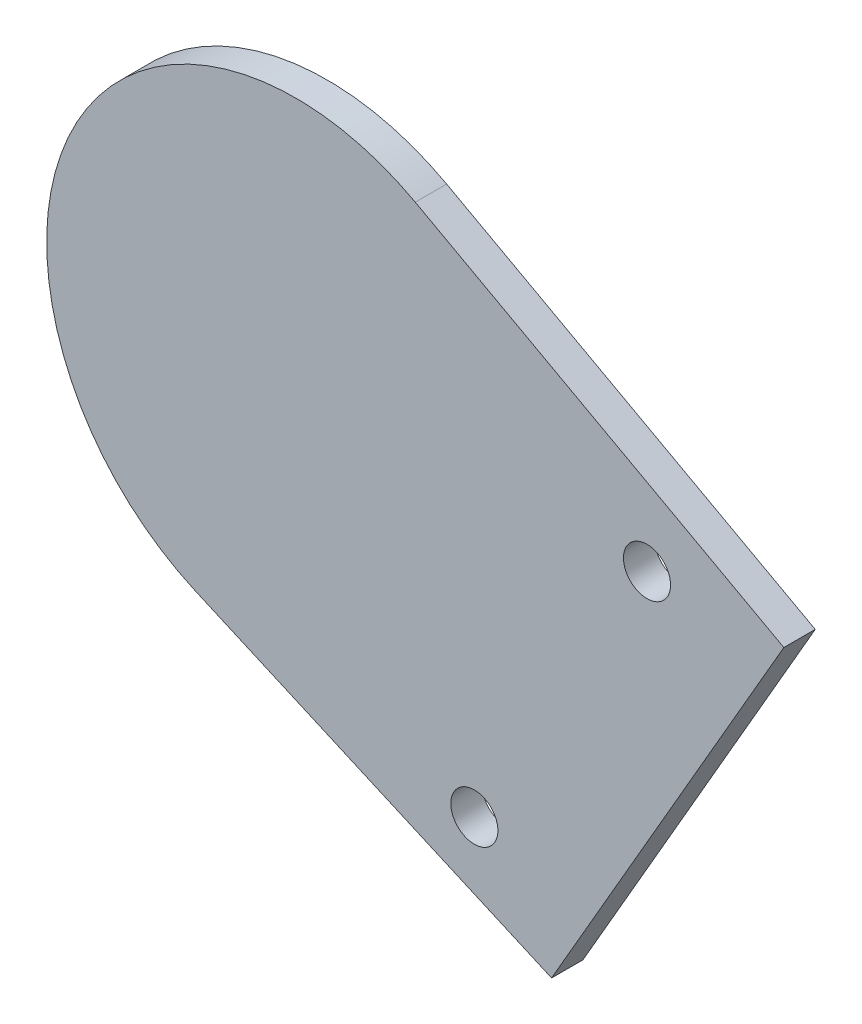
SolidWorks part; units mm, degrees
ref_plane "Front Plane" through (0, 0, 0) normal (0, 0, 1) x (1, 0, 0)
ref_plane "Top Plane" through (0, 0, 0) normal (0, 1, 0) x (1, 0, 0)
ref_plane "Right Plane" through (0, 0, 0) normal (1, 0, 0) x (0, 0, -1)
sketch "Sketch1" plane through (0, 0, 0) normal (0, 0, 1) x (1, 0, 0)
  line L0 (15.7789, 27.3298) -> (13.8682, 28.4329)
  line L1 (7.7451, 26.5416) -> (-0.0719, 29.0062)
  line L2 (13.2451, 36.0678) -> (7.2021, 41.6052)
  line L3 (14.7909, 33.6737) -> (18.2789, 31.6599)
  line L4 (18.2789, 31.6599) -> (24.43, 42.314)
  line L5 (24.43, 42.314) -> (0.9437, 55.145)
  line L6 (9.6278, 16.6758) -> (-13.0737, 26.6885)
  line L7 (9.6278, 16.6758) -> (15.7789, 27.3298)
  line L8 (12.5695, 35.3306) -> (6.2076, 41.1602)
  line L9 (8.0458, 27.4953) -> (-0.1838, 30.0901)
  line L10 (13.082, 29.0509) -> (13.8409, 33.3614)
  line L11 (15.7789, 27.3298) -> (18.2789, 31.6599)
  circle A0 centre (4.7092, 23.0982) radius 1.5
  circle A1 centre (15.7092, 42.1507) radius 1.5
  arc A2 (7.7451, 26.5416) -> (13.8682, 28.4329) centre (9.4391, 31.9144) ccw
  arc A3 (7.2021, 41.6052) -> (-0.0719, 29.0062) centre (-6.6673, 41.2134) ccw
  arc A4 (14.7909, 33.6737) -> (13.2451, 36.0678) centre (9.4391, 31.9144) ccw
  arc A5 (0.9437, 55.145) -> (-13.0737, 26.6885) centre (-6.6673, 41.2134) ccw
  arc A6 (13.8409, 33.3614) -> (12.5695, 35.3306) centre (9.4391, 31.9144) ccw
  arc A7 (6.2076, 41.1602) -> (-0.1838, 30.0901) centre (-6.6673, 41.2134) ccw
  arc A8 (8.0458, 27.4953) -> (13.082, 29.0509) centre (9.4391, 31.9144) ccw
  dimension "D1" = 1
extrude "Boss-Extrude1" add sketch "Sketch1" against normal blind 1 contours L9 A8 L10 A6 L8 A7 region at (-4.2988, 39.8415, 0)
extrude "Boss-Extrude2" add sketch "Sketch1<3>" along normal blind 2 contours L9 A8 L10 A6 L8 A7 | L3 A4 L2 A3 L1 A2 L0 L11 A8 L9 A7 L8 A6 L10 | L5 A5 L6 L7 L0 A2 L1 A3 L2 A4 L3 L4 A0 A1 region at (12.1667, 22.3126, 0) region at (15.0652, 28.3, 0) region at (-4.2988, 39.8415, 0)
sketch "Sketch1<3>" plane through (0, 0, 0) normal (0, 0, 1) x (1, 0, 0) same geometry as "Sketch1"
